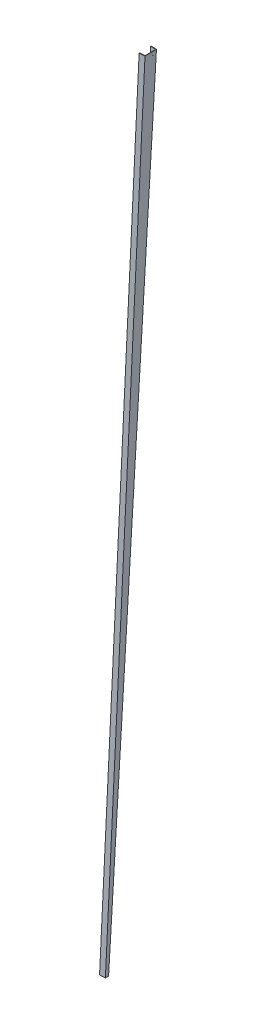
SolidWorks part; units mm, degrees
ref_plane "Front Plane" through (0, 0, 0) normal (0, 0, 1) x (1, 0, 0)
ref_plane "Top Plane" through (0, 0, 0) normal (0, 1, 0) x (1, 0, 0)
ref_plane "Right Plane" through (0, 0, 0) normal (1, 0, 0) x (0, 0, -1)
curve "Curve2"
  spline degree 3 poles (4000, 0, 3.36) (3933.7952, 0, 13.7836) (3801.3288, 0, 34.6398) (3535.8598, 0, 72.9041) (3203.3086, 0, 115.6254) (2803.4291, 0, 159.0217) (2402.8529, 0, 194.3246) (2001.6907, 0, 220.4636) (1599.3709, 0, 237.3526) (1263.2444, 0, 238.5562) (993.9739, 0, 228.1238) (792.1965, 0, 214.0116) (590.7612, 0, 192.5716) (423.6273, 0, 166.9066) (290.5285, 0, 139.3108) (190.9422, 0, 115.3098) (107.85, 0, 83.2401) (41.1412, 0, 57.7125) (-26.5303, 0, -2.7796) (51.7418, 0, -47.9035) (120.8588, 0, -63.3442) (208.0782, 0, -76.9163) (308.6135, 0, -84.9268) (442.4147, 0, -91.4528) (608.5618, 0, -94.255) (807.5001, 0, -93.1942) (1005.8652, 0, -89.7827) (1269.9834, 0, -83.4685) (1600.8258, 0, -74.8684) (1998.599, 0, -63.7434) (2397.4918, 0, -50.4963) (2796.9631, 0, -37.5709) (3197.1451, 0, -25.2391) (3531.1287, 0, -15.9133) (3798.838, 0, -8.6469) (3932.8931, 0, -5.1237) (4000, 0, -3.36) knots 0 0 0 0 0.02488 0.049781 0.099567 0.14934 0.199092 0.248839 0.298568 0.348561 0.373567 0.398591 0.423638 0.448742 0.461353 0.474029 0.486955 0.493558 0.502381 0.511191 0.517824 0.530564 0.54309 0.555505 0.580209 0.604805 0.629344 0.653862 0.702881 0.752206 0.801586 0.851045 0.900581 0.950217 0.975079 1 1 1 1
ref_plane "Plane1" through (0, -15000, 0) normal (0, 1, 0) x (1, 0, 0)
curve "Curve3"
  spline degree 3 poles (1250, -15000, 1.05) (1229.311, -15000, 4.3074) (1187.9152, -15000, 10.8249) (1104.9562, -15000, 22.7825) (1001.0339, -15000, 36.1329) (876.0716, -15000, 49.6943) (750.8915, -15000, 60.7264) (625.5283, -15000, 68.8949) (499.8034, -15000, 74.1727) (394.7639, -15000, 74.5488) (310.6168, -15000, 71.2887) (247.5614, -15000, 66.8786) (184.6129, -15000, 60.1786) (132.3835, -15000, 52.1583) (90.7902, -15000, 43.5346) (59.6694, -15000, 36.0343) (33.7031, -15000, 26.0125) (12.8566, -15000, 18.0352) (-8.2907, -15000, -0.8686) (16.1693, -15000, -14.9698) (37.7684, -15000, -19.7951) (65.0244, -15000, -24.0364) (96.4417, -15000, -26.5396) (138.2546, -15000, -28.579) (190.1756, -15000, -29.4547) (252.3438, -15000, -29.1232) (314.3329, -15000, -28.0571) (396.8698, -15000, -26.0839) (500.2581, -15000, -23.3964) (624.5622, -15000, -19.9198) (749.2162, -15000, -15.7801) (874.051, -15000, -11.7409) (999.1078, -15000, -7.8872) (1103.4777, -15000, -4.9729) (1187.1369, -15000, -2.7022) (1229.0291, -15000, -1.6012) (1250, -15000, -1.05) knots 0 0 0 0 0.02488 0.049781 0.099567 0.14934 0.199092 0.248839 0.298568 0.348561 0.373567 0.398591 0.423638 0.448742 0.461353 0.474029 0.486955 0.493558 0.502381 0.511191 0.517824 0.530564 0.54309 0.555505 0.580209 0.604805 0.629344 0.653862 0.702881 0.752206 0.801586 0.851045 0.900581 0.950217 0.975079 1 1 1 1
sketch "Sketch1" plane through (0, 0, 0) normal (0, 1, 0) x (1, 0, 0)
  line L17 (2600, 43.9641) -> (2600, -176.5868)
  line L18 (600, -192.1843) -> (600, 93.4646)
  line L19 (2500.0525, 43.2029) -> (2499.7923, 35.2071)
  line L20 (2500.3585, -179.0469) -> (2499.7035, -171.0738)
  line L21 (2499.7035, -171.0738) -> (2596, -162.9253)
  line L22 (2499.7923, 35.2071) -> (2596, 32.0935)
  line L23 (2596, 32.0935) -> (2596, -162.9253)
  spline S0 degree 3 poles (600, 89.4646) (602.96, 89.4846) (672.1595, 89.9159) (807.5001, 89.1942) (1005.8652, 85.7827) (1269.9834, 79.4685) (1600.8258, 70.8684) (1998.599, 59.7434) (2331.9077, 48.6743) (2532.4261, 42.1441) (2600, 39.9641) knots 0.57911 0.57911 0.57911 0.57911 0.580209 0.604805 0.629344 0.653862 0.702881 0.752206 0.801586 0.826685 0.826685 0.826685 0.826685
  spline S1 degree 3 poles (2600, -170.5868) (2534.2697, -176.3468) (2334.9532, -192.7488) (2001.6907, -214.4636) (1599.3709, -231.3526) (1263.2444, -232.5562) (993.9739, -222.1238) (795.1742, -208.2199) (663.9659, -194.3608) (600, -186.1843) knots 0.174598 0.174598 0.174598 0.174598 0.199092 0.248839 0.298568 0.348561 0.373567 0.398591 0.42253 0.42253 0.42253 0.42253
  spline S2 degree 3 poles (2600, -176.5868) (2534.2697, -182.3468) (2334.9532, -198.7488) (2001.6907, -220.4636) (1599.3709, -237.3526) (1263.2444, -238.5562) (993.9739, -228.1238) (795.1742, -214.2199) (663.9659, -200.3608) (600, -192.1843) knots 0.174598 0.174598 0.174598 0.174598 0.199092 0.248839 0.298568 0.348561 0.373567 0.398591 0.42253 0.42253 0.42253 0.42253
  spline S3 degree 3 poles (600, 93.4646) (602.96, 93.4846) (672.1595, 93.9159) (807.5001, 93.1942) (1005.8652, 89.7827) (1269.9834, 83.4685) (1600.8258, 74.8684) (1998.599, 63.7434) (2331.9077, 52.6743) (2532.4261, 46.1441) (2600, 43.9641) knots 0.57911 0.57911 0.57911 0.57911 0.580209 0.604805 0.629344 0.653862 0.702881 0.752206 0.801586 0.826685 0.826685 0.826685 0.826685
  spline S4 degree 3 poles (6821.9855, -623.5301) (5697.9832, 343.3422) (4691.0715, 93.6065) (3535.8598, -72.9041) (3203.3086, -115.6254) (2803.4291, -159.0217) (2402.8529, -194.3246) (2001.6907, -220.4636) (1599.3709, -237.3526) (1263.2444, -238.5562) (993.9739, -228.1238) (792.1965, -214.0116) (590.7612, -192.5716) (423.6273, -166.9066) (290.5285, -139.3108) (190.9422, -115.3098) (107.85, -83.2401) (41.1412, -57.7125) (-26.5303, 2.7796) (51.7418, 47.9035) (120.8588, 63.3442) (208.0782, 76.9163) (308.6135, 84.9268) (442.4147, 91.4528) (608.5618, 94.255) (807.5001, 93.1942) (1005.8652, 89.7827) (1269.9834, 83.4685) (1600.8258, 74.8684) (1998.599, 63.7434) (2397.4918, 50.4963) (2796.9631, 37.5709) (3197.1451, 25.2391) (3531.1287, 15.9133) (4797.604, -18.4623) (5930.6427, -40.9757) (6993.8131, -170.658) knots -0.333707 -0.333707 -0.333707 -0.333707 0.02488 0.049781 0.099567 0.14934 0.199092 0.248839 0.298568 0.348561 0.373567 0.398591 0.423638 0.448742 0.461353 0.474029 0.486955 0.493558 0.502381 0.511191 0.517824 0.530564 0.54309 0.555505 0.580209 0.604805 0.629344 0.653862 0.702881 0.752206 0.801586 0.851045 0.900581 0.950217 0.975079 1.370912 1.370912 1.370912 1.370912 only from (4000, -3.36) to (4000, 3.36) construction
  spline S5 degree 3 poles (4000, -3.36) (3933.7952, -13.7836) (3801.3288, -34.6398) (3535.8598, -72.9041) (3203.3086, -115.6254) (2803.4291, -159.0217) (2402.8529, -194.3246) (2001.6907, -220.4636) (1599.3709, -237.3526) (1263.2444, -238.5562) (993.9739, -228.1238) (792.1965, -214.0116) (590.7612, -192.5716) (423.6273, -166.9066) (290.5285, -139.3108) (190.9422, -115.3098) (107.85, -83.2401) (41.1412, -57.7125) (-26.5303, 2.7796) (51.7418, 47.9035) (120.8588, 63.3442) (208.0782, 76.9163) (308.6135, 84.9268) (442.4147, 91.4528) (608.5618, 94.255) (807.5001, 93.1942) (1005.8652, 89.7827) (1269.9834, 83.4685) (1600.8258, 74.8684) (1998.599, 63.7434) (2397.4918, 50.4963) (2796.9631, 37.5709) (3197.1451, 25.2391) (3531.1287, 15.9133) (3798.838, 8.6469) (3932.8931, 5.1237) (4000, 3.36) knots 0 0 0 0 0.02488 0.049781 0.099567 0.14934 0.199092 0.248839 0.298568 0.348561 0.373567 0.398591 0.423638 0.448742 0.461353 0.474029 0.486955 0.493558 0.502381 0.511191 0.517824 0.530564 0.54309 0.555505 0.580209 0.604805 0.629344 0.653862 0.702881 0.752206 0.801586 0.851045 0.900581 0.950217 0.975079 1 1 1 1
  point P0 (2600, -162.5868)
  point P6 (2600, -176.5868)
  point P7 (2600, 43.9641)
  point P8 (1600, -234.76)
  point P12 (2600, 31.9641)
  point P14 (600, 93.4646)
  dimension "D1" = 2600
  dimension "D2" = 1000
  dimension "D3" = 4
  dimension "D4" = 1000
  dimension "D5" = 42.5757
  dimension "D6" = 6
  dimension "D7" = 234.76
  dimension "D8" = 43.9641
  dimension "D9" = 285.6489
  dimension "D10" = 220.5509
  dimension "D11" = 6
  dimension "D12" = 4
  dimension "D13" = 100
  dimension "D14" = 8
  dimension "D15" = 8
  dimension "D16" = 8
  dimension "D17" = 4
  dimension "D18" = 274.7241
  dimension "D19" = 8
  dimension "100mm" = 100
sketch "Sketch2" plane through (0, -15000, 0) normal (0, 1, 0) x (1, 0, 0)
  line L15 (1912.5, -147.6587) -> (1912.5, -216.5809)
  line L16 (1287.5, -132.1898) -> (1287.5, -221.4551)
  line L18 (1812.5532, -148.3964) -> (1812.2912, -156.3921)
  line L20 (1812.2912, -156.3921) -> (1908.5, -159.5283)
  line L21 (1812.8085, -218.43) -> (1812.2527, -210.4493)
  line L22 (1812.2527, -210.4493) -> (1908.5, -202.8948)
  line L23 (1908.5, -159.5283) -> (1908.5, -202.8948)
  spline S1 degree 3 poles (1912.5, -216.5809) (1891.9593, -218.3809) (1829.6729, -223.5065) (1725.5283, -230.2924) (1599.8034, -235.5702) (1494.7639, -235.9463) (1410.6168, -232.6862) (1348.4919, -228.3412) (1307.4893, -224.0103) (1287.5, -221.4551) knots 0.174598 0.174598 0.174598 0.174598 0.199092 0.248839 0.298568 0.348561 0.373567 0.398591 0.42253 0.42253 0.42253 0.42253
  spline S2 degree 3 poles (1287.5, -132.1898) (1288.425, -132.1836) (1310.0498, -132.0488) (1352.3438, -132.2743) (1414.3329, -133.3404) (1496.8698, -135.3136) (1600.2581, -138.0011) (1724.5622, -141.4777) (1828.7212, -144.9368) (1891.3832, -146.9775) (1912.5, -147.6587) knots 0.57911 0.57911 0.57911 0.57911 0.580209 0.604805 0.629344 0.653862 0.702881 0.752206 0.801586 0.826685 0.826685 0.826685 0.826685
  spline S4 degree 3 poles (1912.5, -210.5809) (1891.9593, -212.3809) (1829.6729, -217.5065) (1725.5283, -224.2924) (1599.8034, -229.5702) (1494.7639, -229.9463) (1410.6168, -226.6862) (1348.4919, -222.3412) (1307.4893, -218.0103) (1287.5, -215.4551) knots 0.174598 0.174598 0.174598 0.174598 0.199092 0.248839 0.298568 0.348561 0.373567 0.398591 0.42253 0.42253 0.42253 0.42253
  spline S5 degree 3 poles (1287.5, -136.1898) (1288.425, -136.1836) (1310.0498, -136.0488) (1352.3438, -136.2743) (1414.3329, -137.3404) (1496.8698, -139.3136) (1600.2581, -142.0011) (1724.5622, -145.4777) (1828.7212, -148.9368) (1891.3832, -150.9775) (1912.5, -151.6587) knots 0.57911 0.57911 0.57911 0.57911 0.580209 0.604805 0.629344 0.653862 0.702881 0.752206 0.801586 0.826685 0.826685 0.826685 0.826685
  point P0 (1600, -234.76)
  point P9 (1912.5, -159.6587)
  point P19 (1912.5, -202.5809)
  dimension "D1" = 312.5
  dimension "D2" = 6
  dimension "D3" = 89.2653
  dimension "D4" = 6
  dimension "D5" = 312.5
  dimension "D6" = 13.3049
  dimension "D7" = 68.9222
  dimension "D8" = 4
  dimension "D9" = 4
  dimension "D10" = 100
  dimension "D11" = 8
  dimension "D12" = 4
  dimension "D13" = 8
  dimension "D14" = 8
  dimension "D15" = 100
  dimension "D16" = 8
extrude "Boss-Extrude1" add sketch "Sketch1" against normal blind 6 contours S1 L17 S0 L19 L22 L23 L21 L20 region at (2597.5617, 0, 65.3114)
extrude "Boss-Extrude2" add sketch "Sketch2" along normal blind 6 separate body contours S5 L18 L20 L23 L22 L21 S4 L15 region at (1911.2771, -15000, 181.1198)
loft "Loft1" add section face at (2548.9692, -6, 65.9145) section face at (1861.4722, -14994, 181.5968) connector at (2596, -6, -32.0935) connector at (1908.5, -14994, 159.5283)
hole_wizard "Ø4.0mm Dowel Hole1" positions "Sketch3" profile "Sketch4" hole size "Ø4.0" standard "ISO" end condition through all
sketch "Sketch3" plane through (2592.5775, -80.6136, -62.9537) normal (-0.9989, 0.0458, 0) x (-0.0458, -0.9989, 0)
  point P0 (-14.6923, 128.5294)
  point P1 (-14.6923, 208.5294)
  point P2 (-14.6923, 168.5294)
  point P3 (-14.6923, 48.5294)
  point P4 (-14.6923, 88.5294)
sketch "Sketch4" plane through (2593.2507, -65.9368, 65.5757) normal (0, 0, 1) x (-0.0458, -0.9989, 0)
  line L0 (0, 0) -> (0, 691.0487)
  line L1 (0, 691.0487) -> (2, 691.0487)
  line L2 (2, 691.0487) -> (2, 0)
  line L3 (2, 0) -> (0, 0)
  line L4 (0, -6.35) -> (0, 107.95) construction
  dimension "Thru Hole Dia." = 4
  dimension "Thru Hole Depth" = 691.0487
